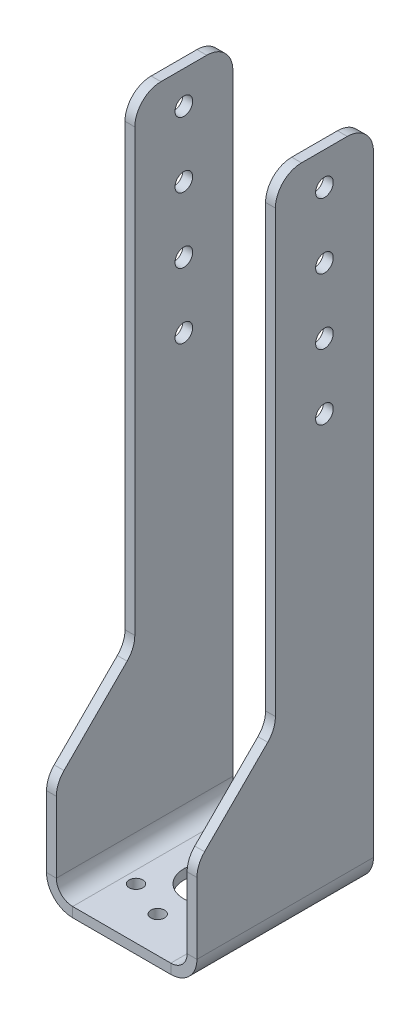
SolidWorks part; units mm, degrees
note: The reader was unsure of these and kept them because the rebuilt part matched: bend radius of "Base-Flange1", "BaseBend1", "BaseBend2".
material "2024 Alloy (SN)"
ref_plane "Front Plane" through (0, 0, 0) normal (0, 0, 1) x (1, 0, 0)
ref_plane "Top Plane" through (0, 0, 0) normal (0, 1, 0) x (1, 0, 0)
ref_plane "Right Plane" through (0, 0, 0) normal (1, 0, 0) x (0, 0, -1)
sketch "Sketch1" plane through (0, 0, 0) normal (0, 0, 1) x (1, 0, 0)
  line L0 (-10, 100) -> (-10, 0)
  line L1 (-10, 0) -> (10, 0)
  line L2 (10, 0) -> (10, 100)
  point P2 (0, 0)
  dimension "D1" = 100
  dimension "D2" = 20
sheet metal parameters "Sheet-Metal1" thickness 1.5 parameters "D1"=2.5
base flange "Base-Flange1" sketch "Sketch1" end condition mid plane depth 27 reverse direction no thickness 1.5 reverse thickness direction no bend radius 2.5
bend "BaseBend1" bend radius 2.5 bend angle 90 parameters "D5"=1
bend "BaseBend2" bend radius 2.5 bend angle 90 parameters "D5"=2
sketch "Sketch5" plane through (0, 0, 0) normal (0, 1, 0) x (1, 0, 0)
  circle A0 centre (0, 0) radius 4
  circle A1 centre (0, 8) radius 1.05
  circle A2 centre (5.6569, 5.6569) radius 1.05
  circle A3 centre (8, 0) radius 1.05
  circle A4 centre (5.6569, -5.6569) radius 1.05
  circle A5 centre (0, -8) radius 1.05
  circle A6 centre (-5.6569, -5.6569) radius 1.05
  circle A7 centre (-8, 0) radius 1.05
  circle A8 centre (-5.6569, 5.6569) radius 1.05
  dimension "D1" = 8
  dimension "D2" = 2.1
  dimension "D3" = 8
  dimension "D4" = 8
extrude "Cut-Extrude1" cut sketch "Sketch5" against normal blind 10 contours A0 | A8 | A1 | A2 | A4 | A5 | A6 normal cut yes
sketch "Sketch6" plane through (0, 0, 0) normal (1, 0, 0) x (0, 0, -1)
  line L0 (-1.5, 100) -> (-1.5, 27)
  line L1 (-13.5, 100) -> (13.5, 100) construction
  line L2 (-1.5, 27) -> (-13.5, 15)
  line L3 (-13.5, 2.5) -> (-13.5, 100) construction
  line L4 (-13.5, 15) -> (-13.5, 100)
  line L5 (-13.5, 100) -> (-1.5, 100)
  line L6 (13.5, 2.5) -> (13.5, 100) construction
  dimension "D1" = 45
  dimension "D2" = 15
  dimension "D3" = 15
extrude "Cut-Extrude2" cut sketch "Sketch6" against normal through all both and the other way through all normal cut yes
sketch "Sketch7" plane through (11.5, 0, 0) normal (1, 0, 0) x (0, 0, -1)
  line L0 (-1.5, 100) -> (13.5, 100) construction
  line L1 (13.5, 2.5) -> (13.5, 100) construction
  circle A0 centre (6, 95) radius 1.35
  circle A1 centre (6, 85) radius 1.35
  circle A2 centre (6, 75) radius 1.35
  circle A3 centre (6, 65) radius 1.35
  dimension "D1" = 5
  dimension "D2" = 7.5
  dimension "D3" = 2.7
  dimension "D4" = 4
extrude "Cut-Extrude3" cut sketch "Sketch7" against normal through all both and the other way through all normal cut yes
fillet "Fillet1" radius 4 8 edges at (10.75, 100, 1.5) (-10.75, 100, 1.5) (-10.75, 100, -13.5) (10.75, 100, -13.5) (-10.75, 27, 1.5) (-10.75, 15, 13.5) (10.75, 15, 13.5) (10.75, 27, 1.5)
flat pattern "Flat-Pattern1" [suppressed]
sketch "Bend-Lines1" plane through (16, 0, 0) normal (-1, 0, 0) x (0, 0, 1)
  line L0 (13.5, -32.0343) -> (-13.5, -32.0343) construction
  line L1 (13.5, 1.3219) -> (-13.5, 1.3219) construction
  line L2 (13.5, -32.0343) -> (-13.5, -32.0343) construction
  line L3 (13.5, 1.3219) -> (-13.5, 1.3219) construction
sketch3d "Bounding-Box1" [suppressed]
  line L0 (-27, 92, 0) -> (-27, -122.7124, 0) construction
  line L1 (0, 92, 0) -> (0, -122.7124, 0) construction
  line L2 (-27, 92, 0) -> (0, 92, 0) construction
  line L3 (-27, -122.7124, 0) -> (0, -122.7124, 0) construction
bend of the flat pattern "Flatten-<BaseBend1>1"
bend of the flat pattern "Flatten-<BaseBend2>1"
